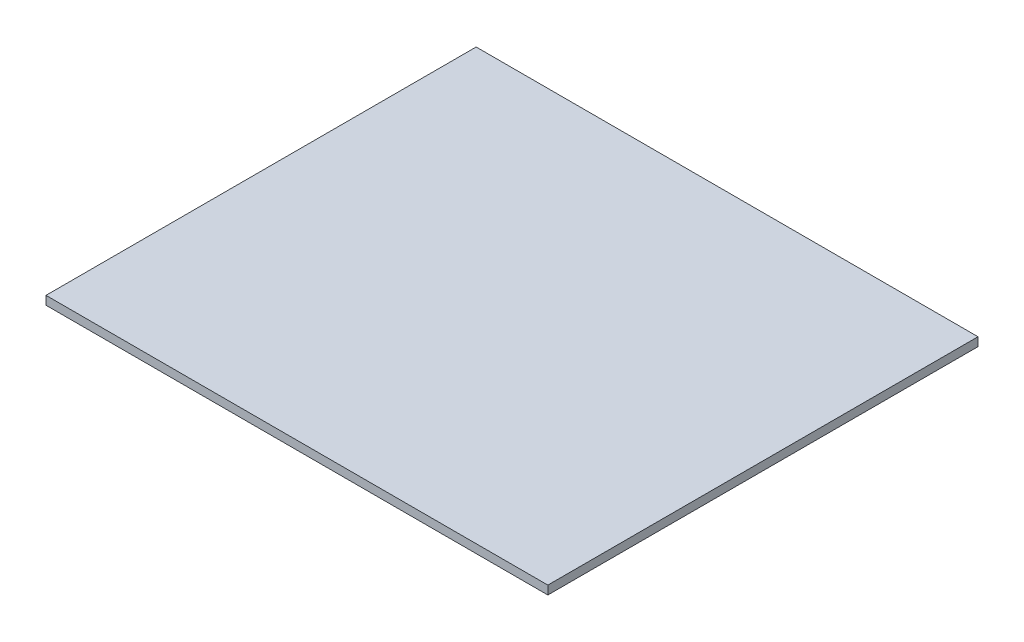
SolidWorks part; units mm, degrees
material "Concreto"
ref_plane "Plano frontal" through (0, 0, 0) normal (0, 0, 1) x (1, 0, 0)
ref_plane "Plano superior" through (0, 0, 0) normal (0, 1, 0) x (1, 0, 0)
ref_plane "Plano direito" through (0, 0, 0) normal (1, 0, 0) x (0, 0, -1)
sketch "Esboço1" plane through (0, 0, 0) normal (0, 1, 0) x (1, 0, 0)
  line L0 (-1750, 0) -> (1750, 0) construction
  line L1 (-1750, 1500) -> (1750, 1500)
  line L2 (-1750, 1500) -> (-1750, -1500)
  line L3 (-1750, -1500) -> (1750, -1500)
  line L4 (1750, 1500) -> (1750, -1500)
  line L5 (-1750, 1500) -> (1750, -1500) construction
  line L6 (-1750, -1500) -> (1750, 1500) construction
  point P0 (0, 0)
  dimension "D1" = 3000
  dimension "D2" = 3500
extrude "Ressalto-extrusão1" add sketch "Esboço1" along normal blind 60
